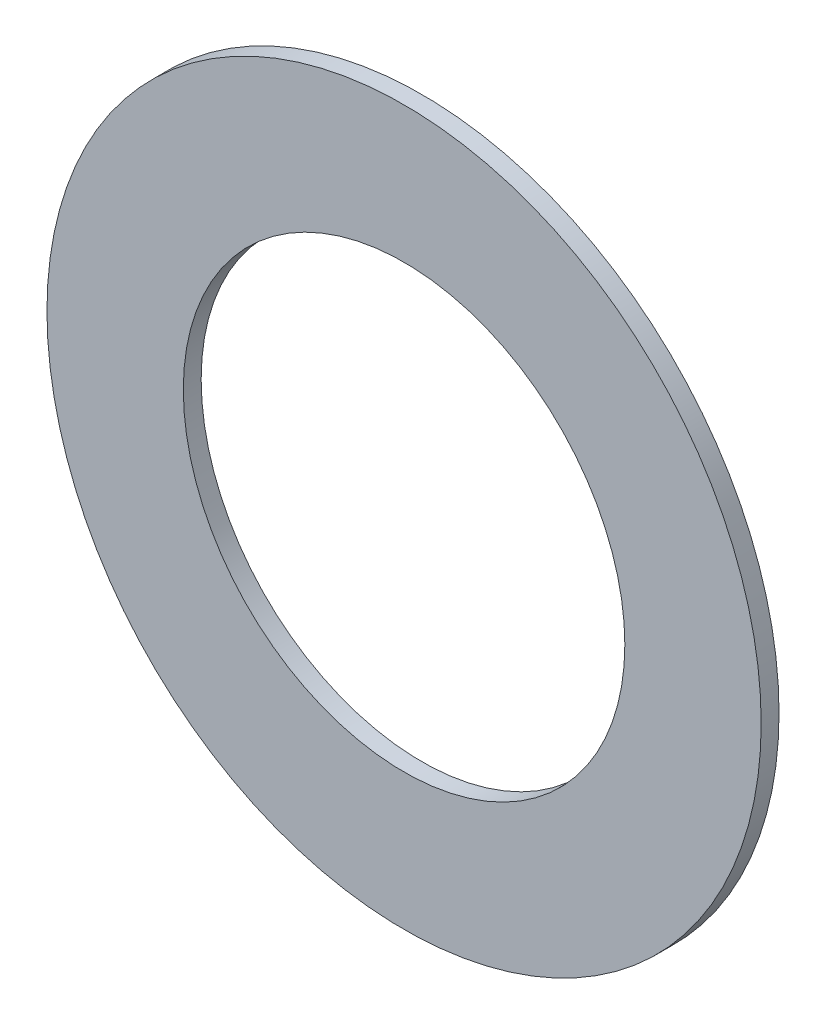
SolidWorks part; units mm, degrees
ref_plane "Front Plane" through (0, 0, 0) normal (0, 0, 1) x (1, 0, 0)
ref_plane "Top Plane" through (0, 0, 0) normal (0, 1, 0) x (1, 0, 0)
ref_plane "Right Plane" through (0, 0, 0) normal (1, 0, 0) x (0, 0, -1)
sketch "Sketch1" plane through (0, 0, 0) normal (0, 0, 1) x (1, 0, 0)
  circle A0 centre (0, 0) radius 63.5
  circle A1 centre (0, 0) radius 39.2557
  dimension "D1" = 78.5114
  dimension "D2" = 127
extrude "Boss-Extrude1" add sketch "Sketch1" along normal blind 3.175
equation "\"AIRFRAME_OD\"= 5.15in"
equation "\"AIRFRAME_ID\"= 5.00in"
equation "\"FLAT_T\"= 0.125in"
equation "\"COUPLER_OD\"= 4.998in"
equation "\"COUPLER_ID\"= 4.88in"
equation "\"NOSE_EXP_L\"= 27in"
equation "\"NOSE_SHOULDER_L\"= 5in"
equation "\"MAIN_L\"= 30in"
equation "\"RECO_COUP_L\"= 10in"
equation "\"RECO_SWITCH_L\"= 2in"
equation "\"RECO_ROD_X\"= 3.5in"
equation "\"DROGUE_L\"= 20in"
equation "\"ATS_FORE_COUP_L\"= 5.5in"
equation "\"ATS_AFT_COUP_L\"= 4.5in"
equation "\"ATS_ROD_X\"= 3in"
equation "\"LOWER_L\"= 30in"
equation "\"FIN_ROOT\"= 8in"
equation "\"FIN_X\"= 0.75in"
equation "\"FIN_N\"= 4"
equation "\"MOTOR_OD\"= 3.091in"
equation "\"MOTOR_ID\"= 3.00in"
equation "\"MOTOR_L\"= 14in"
equation "\"CR_AFT_X\"= 0.5in"
equation "\"CR_FORE_X\"= 9.25in"
equation "\"D1@Boss-Extrude1\"=\"FLAT_T\""
equation "\"D1@Sketch1\"=\"MOTOR_OD\""
equation "\"D2@Sketch1\"=\"AIRFRAME_ID\""
equation "\"MOTOR_LOWER_X\"= 2in"
